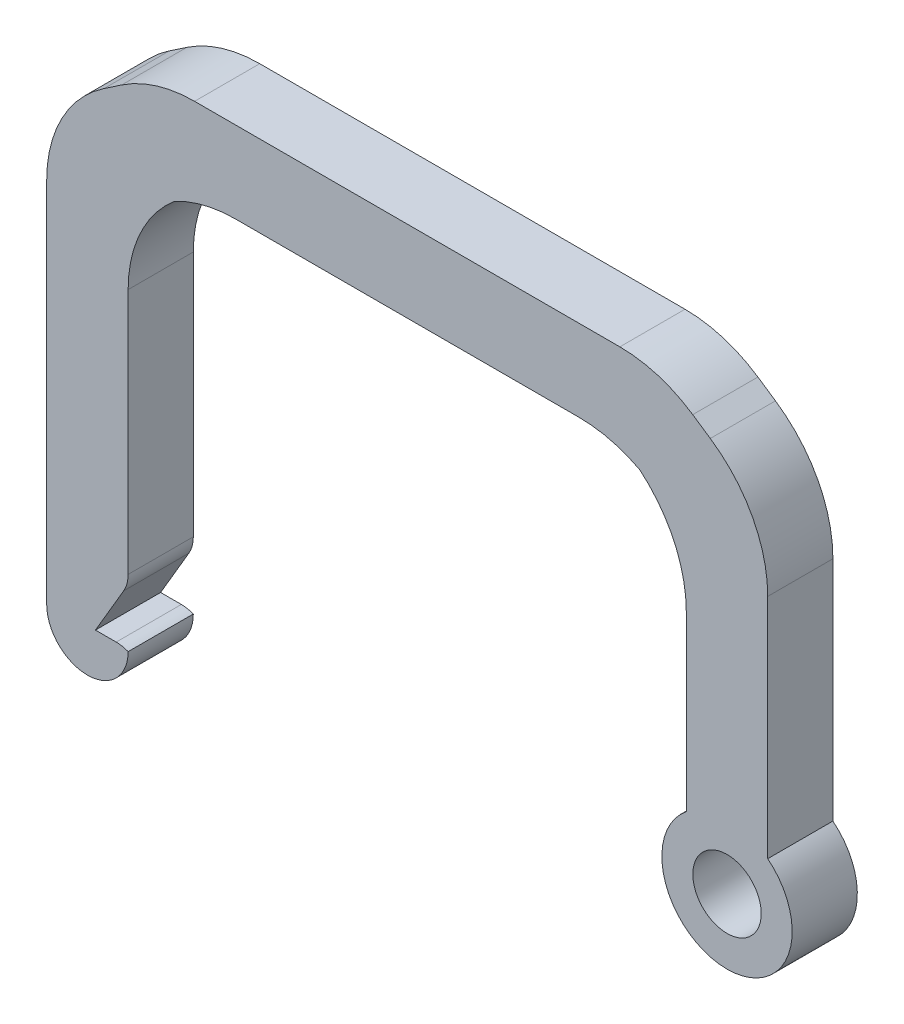
SolidWorks part; units mm, degrees
ref_plane "Alzado" through (0, 0, 0) normal (0, 0, 1) x (1, 0, 0)
ref_plane "Planta" through (0, 0, 0) normal (0, 1, 0) x (1, 0, 0)
ref_plane "Vista lateral" through (0, 0, 0) normal (1, 0, 0) x (0, 0, -1)
sketch "Croquis3" plane through (0, 0, 0) normal (0, 0, 1) x (1, 0, 0)
  line L0 (-15.5, 0) -> (15.5, 0)
  line L1 (-15.5, 0) -> (-22.1323, -4.4735)
  line L2 (-22.1323, -4.4735) -> (-22.1323, -22.796)
  line L3 (-22.1323, -22.796) -> (-17.1323, -22.796)
  line L4 (-17.1323, -22.796) -> (-17.1323, -7.796)
  line L5 (-17.1323, -7.796) -> (-12.9871, -5)
  line L6 (-12.9871, -5) -> (12.9871, -5)
  line L7 (12.9871, -5) -> (17.1323, -7.796)
  line L8 (17.1323, -7.796) -> (17.1323, -22.796)
  line L9 (17.1323, -22.796) -> (22.1323, -22.796)
  line L10 (22.1323, -22.796) -> (22.1323, -4.4735)
  line L11 (22.1323, -4.4735) -> (15.5, 0)
  point P4 (0, 0)
  dimension "D1" = 31
  dimension "D2" = 5
  dimension "D3" = 5
  dimension "D4" = 5
  dimension "D5" = 5
  dimension "D6" = 124
  dimension "D7" = 124
  dimension "D8" = 124
  dimension "D9" = 124
  dimension "D10" = 8
  dimension "D11" = 8
  dimension "D12" = 5
  dimension "D13" = 15
  dimension "D14" = 15
extrude "Saliente-Extruir4" add sketch "Croquis3" along normal blind 4
fillet "Redondeo1" radius 8 8 edges at (-12.9871, -5, 2) (-17.1323, -7.796, 2) (17.1323, -7.796, 2) (12.9871, -5, 2) (22.1323, -4.4735, 2) (15.5, 0, 2) (-15.5, 0, 2) (-22.1323, -4.4735, 2)
sketch "Croquis4" plane through (0, 0, 4) normal (0, 0, 1) x (1, 0, 0)
  line L0 (19.6323, -22.796) -> (19.6323, -25.796) construction
  line L1 (17.1323, -22.796) -> (22.1323, -22.796) construction
  circle A0 centre (19.6323, -25.796) radius 4
  dimension "D1" = 8
  dimension "D2" = 3
extrude "Saliente-Extruir5" add sketch "Croquis4" against normal through all
sketch "Croquis5" plane through (0, 0, 4) normal (0, 0, 1) x (1, 0, 0)
  circle A0 centre (19.6323, -25.796) radius 2.1
  dimension "D1" = 4.2
extrude "Cortar-Extruir1" cut sketch "Croquis5" against normal blind 10
sketch "Croquis6" plane through (0, 0, 4) normal (0, 0, 1) x (1, 0, 0)
  line L0 (-22.1323, -22.796) -> (-22.1323, -33.796)
  line L1 (-22.1323, -33.796) -> (-17.1323, -33.796)
  line L2 (-17.1323, -33.796) -> (-17.1323, -22.796)
  line L3 (-17.1323, -22.796) -> (-22.1323, -22.796)
  dimension "D1" = 11
extrude "Saliente-Extruir6" add sketch "Croquis6" against normal through all
fillet "Redondeo2" radius 2.5 2 edges at (-17.1323, -33.796, 2) (-22.1323, -33.796, 2)
sketch "Croquis8" plane through (0, 0, 4) normal (0, 0, 1) x (1, 0, 0)
  line L0 (-17.1323, -31.1563) -> (-19.1396, -31.1563)
  line L1 (-17.1323, -31.296) -> (-17.1323, -12.0496) construction
  line L2 (-19.1396, -31.1563) -> (-17.1323, -27.7351)
  line L3 (-17.1323, -27.7351) -> (-17.1323, -31.1563)
extrude "Cortar-Extruir3" cut sketch "Croquis8" against normal blind 10
fillet "Redondeo5" radius 2 1 edges at (-17.1323, -27.7351, 2)
fillet "Redondeo6" radius 2 1 edges at (-17.1323, -31.1563, 2)
